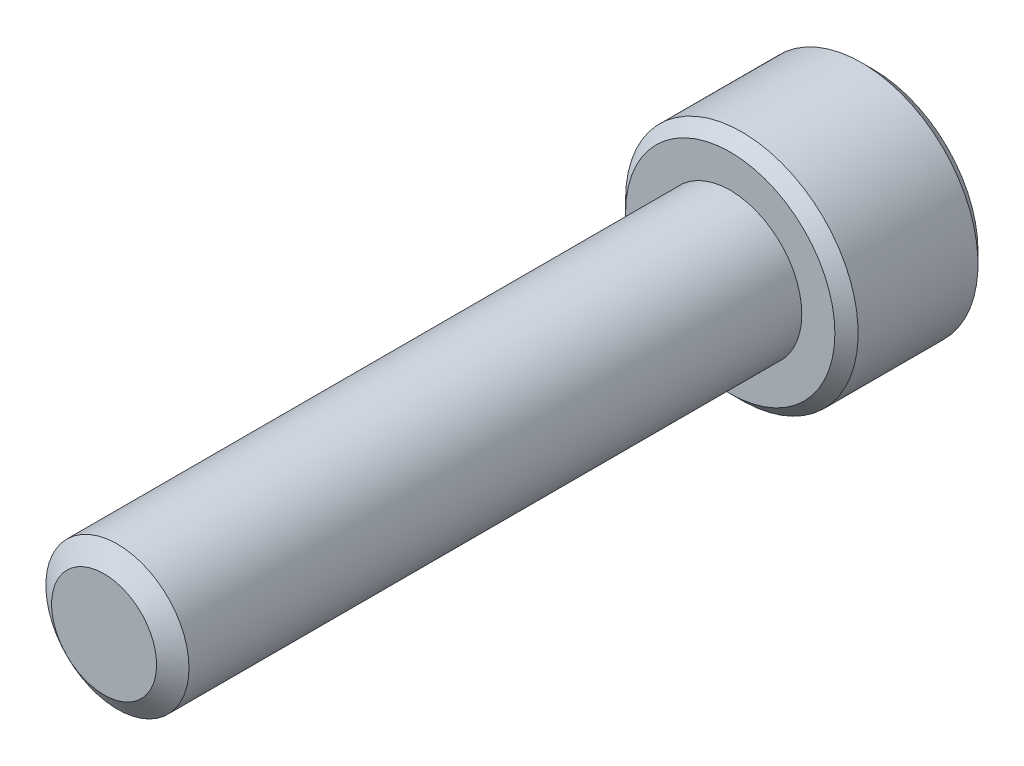
SolidWorks part; units mm, degrees
other "DetailItem1"
ref_plane "Front Plane" through (0, 0, 0) normal (0, 0, 1) x (1, 0, 0)
ref_plane "Top Plane" through (0, 0, 0) normal (0, 1, 0) x (1, 0, 0)
ref_plane "Right Plane" through (0, 0, 0) normal (1, 0, 0) x (0, 0, -1)
sketch "Sketch1" plane through (0, 0, 0) normal (0, 0, 1) x (1, 0, 0)
  circle A0 centre (0, 0) radius 4
  dimension "OD" = 8
extrude "Extrude1" add sketch "Sketch1" against normal blind 35
sketch "Sketch2" plane through (0, 0, 0) normal (0, 0, 1) x (1, 0, 0)
  circle A0 centre (0, 0) radius 4 construction
  circle A1 centre (0, 0) radius 4
curve "Helix/Spiral1" pitch 1.25 height 36.25 turns 29 parameters "pitch"=1.25
sketch "Sketch3" plane through (0, 0, 0) normal (1, 0, 0) x (0, 0, -1)
  line L0 (-1.0938, 4) -> (-0.625, 3.1881)
  line L1 (-0.625, 3.1881) -> (-0.4688, 3.1881)
  line L2 (-0.4688, 3.1881) -> (0, 4)
  line L3 (-1.0938, 4) -> (0, 4)
  line L4 (-0.5469, 4) -> (-0.5469, 3.1881) construction
  line L5 (-0.8594, 3.5941) -> (-0.2344, 3.5941) construction
  line L6 (0, 4) -> (0, -4) construction
  dimension "D1" = 0.1562
  dimension "D2" = 0.625
  dimension "D3" = 60
sweep "Cut-Sweep1" [suppressed] cut profiles "Sketch3" path "Helix/Spiral1"
sketch "Sketch4" plane through (0, 0, 0) normal (1, 0, 0) x (0, 0, -1)
  line L0 (0.7464, 4) -> (0, 2.9341)
  line L1 (0, 2.9341) -> (0, 4)
  line L2 (0.7464, 4) -> (0, 4)
  line L3 (-1.0938, 4) -> (0, 4) construction
  line L4 (0, 0) -> (7.0209, 0) construction
  dimension "D1" = 55
  dimension "D2" = 0.254
revolve "Cut-Revolve1" cut sketch "Sketch4" angle 360 about L4
sketch "Sketch6" plane through (0, 0, -35) normal (0, 0, -1) x (-1, 0, 0)
  circle A0 centre (0, 0) radius 6.5
  dimension "head dia" = 13
extrude "Extrude2" add sketch "Sketch6" along normal blind 8
sketch "Sketch7" plane through (0, 0, -43) normal (0, 0, -1) x (-1, 0, 0)
  line L1 (0, 3.4641) -> (-3, 1.7321)
  line L2 (-3, 1.7321) -> (-3, -1.7321)
  line L3 (-3, -1.7321) -> (0, -3.4641)
  line L4 (0, -3.4641) -> (3, -1.7321)
  line L5 (3, -1.7321) -> (3, 1.7321)
  line L6 (3, 1.7321) -> (0, 3.4641)
  circle A0 centre (0, 0) radius 3 construction
  dimension "hex dia" = 6
extrude "Cut-Extrude1" cut sketch "Sketch7" against normal blind 4.5
sketch "Sketch8" plane through (0, 0, -43) normal (0, 0, -1) x (-1, 0, 0)
  circle A0 centre (0, 0) radius 3.4641
extrude "Cut-Extrude2" cut sketch "Sketch8" against normal through all draft 45
chamfer "Chamfer1" distance 0.65 angle 45 2 edges at (-6.5, 0, -43) (-6.5, 0, -35)
sketch "Sketch10" plane through (0, 0, -35) normal (0, 0, 1) x (1, 0, 0)
  circle A1 centre (0, 0) radius 4
  circle A2 centre (0, 0) radius 4
  dimension "D1" = 0
ref_plane "Plane1" through (0, 0, 0) normal (0, 0, 1) x (1, 0, 0)
extrude "partial thread" [suppressed] add sketch "Sketch10" along normal up to surface (57 mm away) separate body up to plane "Plane1"
chamfer "Chamfer2" [suppressed] distance 0.16 angle 45
combine bodies "Combine1" [suppressed] operation type add bodies to combine 107 108
sketch "Sketch9" plane through (0, 0, 0) normal (1, 0, 0) x (0, 0, -1)
  line L0 (0, 4) -> (0, -4) construction
  line L1 (3.125, 4) -> (3.125, -4) construction
  dimension "D1" = 3.125
equation "\"D3@Helix/Spiral1\" = \"screw length@Extrude1\"+\"pitch@Helix/Spiral1\""
equation "\"D1@Sketch3\" = \"pitch@Helix/Spiral1\"*.125"
equation "\"D2@Sketch3\" = \"pitch@Helix/Spiral1\"*.5"
equation "\"D1@Cut-Extrude1\" = \"hex dia@Sketch7\"*.75"
equation "\"D1@Chamfer1\" = \"head dia@Sketch6\"*.05"
equation "\"D1@Sketch9\" = \"pitch@Helix/Spiral1\"*2.5"
equation "\"D1@Chamfer2\"=\"OD@Sketch1\"*.02"
